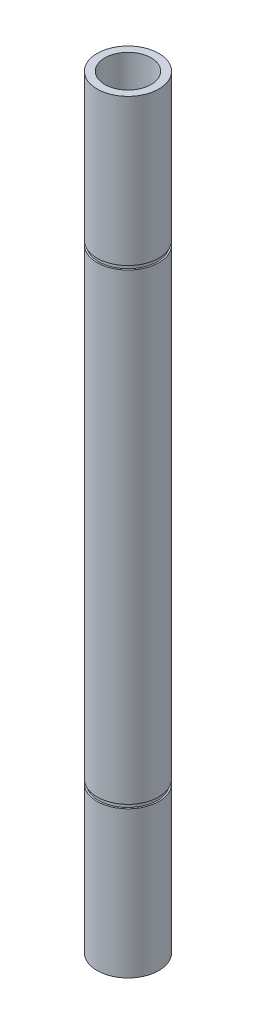
SolidWorks part; units mm, degrees
material "1060 Alloy"
ref_plane "Front Plane" through (0, 0, 0) normal (0, 0, 1) x (1, 0, 0)
ref_plane "Top Plane" through (0, 0, 0) normal (0, 1, 0) x (1, 0, 0)
ref_plane "Right Plane" through (0, 0, 0) normal (1, 0, 0) x (0, 0, -1)
sketch "Sketch1" plane through (0, 0, 0) normal (0, 0, 1) x (1, 0, 0)
  line L0 (0, 64.3023) -> (0, -80.2699) construction
  line L1 (-3, 49.5) -> (-4, 49.5)
  line L2 (-4, 49.5) -> (-4, 30.5)
  line L3 (-4, 30.5) -> (-3.8, 30.5)
  line L4 (-3.8, 30.5) -> (-3.8, 30)
  line L5 (-3.8, 30) -> (-4, 30)
  line L6 (-30.6471, 0) -> (35.9901, 0) construction
  line L7 (-4, 30) -> (-4, -30)
  line L8 (-3.8, -30) -> (-4, -30)
  line L9 (-3.8, -30.5) -> (-3.8, -30)
  line L10 (-4, -30.5) -> (-3.8, -30.5)
  line L11 (-4, -49.5) -> (-4, -30.5)
  line L12 (-3, -49.5) -> (-4, -49.5)
  line L13 (-3, 49.5) -> (-3, -49.5)
  point P11 (-4, 40)
  point P14 (-4, 0)
  dimension "D1" = 99
  dimension "D2" = 8
  dimension "D3" = 0.5
  dimension "D4" = 0.2
  dimension "D5" = 19
  dimension "D6" = 1
revolve "Revolve2" add sketch "Sketch1" angle 360 about L0
